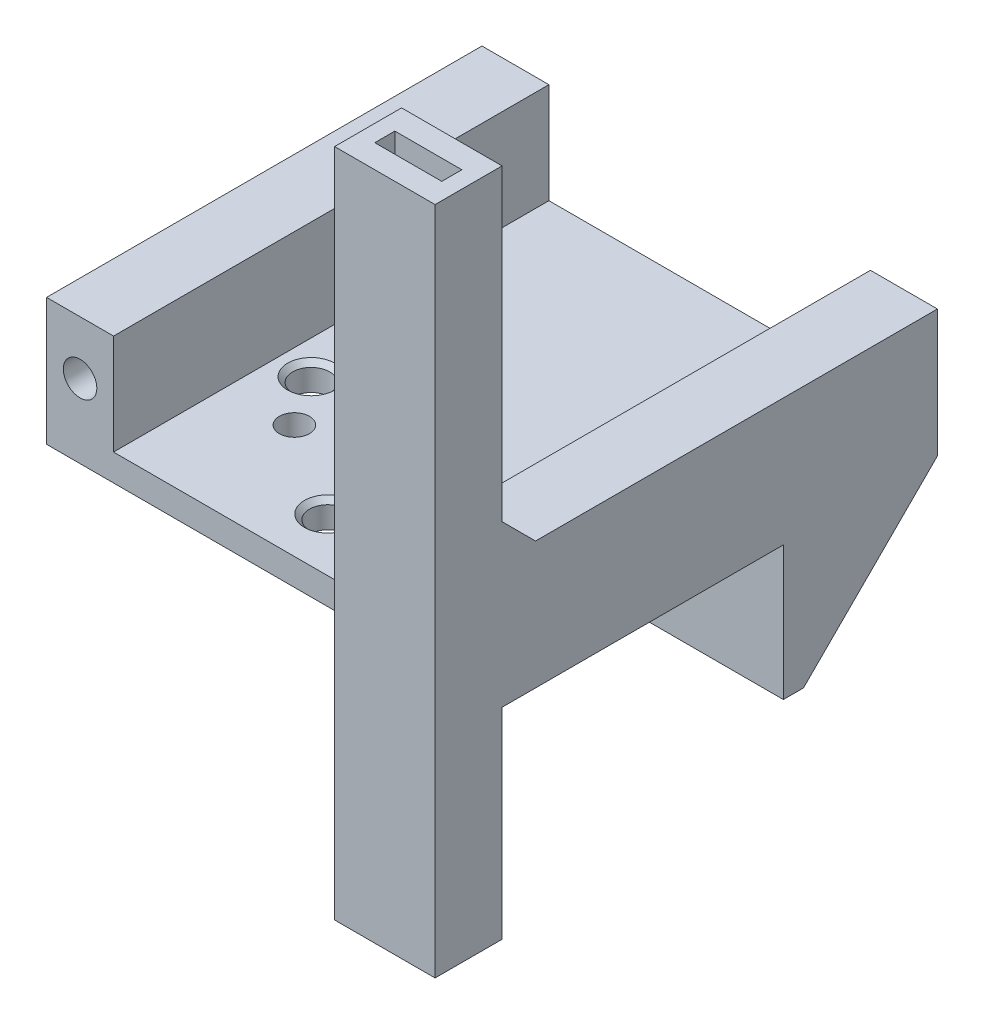
SolidWorks part; units mm, degrees
material "PET"
ref_plane "Front Plane" through (0, 0, 0) normal (0, 0, 1) x (1, 0, 0)
ref_plane "Top Plane" through (0, 0, 0) normal (0, 1, 0) x (1, 0, 0)
ref_plane "Right Plane" through (0, 0, 0) normal (1, 0, 0) x (0, 0, -1)
sketch "Sketch1" plane through (0, 0, 0) normal (0, 1, 0) x (1, 0, 0)
  line L0 (-30, 15) -> (30, 15) construction
  line L2 (-34, 0) -> (-34, 40)
  line L3 (-34, 40) -> (34, 40)
  line L4 (34, 0) -> (34, 40)
  line L5 (0, 0) -> (34, 40) construction
  line L6 (-34, 40) -> (0, 0) construction
  line L7 (-34, 22.5) -> (34, 22.5) construction
  line L8 (-34, 0) -> (-34, -2)
  line L11 (-34, -2) -> (34, -2)
  line L12 (34, -2) -> (34, 0)
  line L13 (-34, 0) -> (34, 0) construction
  line L14 (0, 0) -> (0, 27.8808) construction
  circle A0 centre (-19, 22.5) radius 2.75
  circle A1 centre (19, 22.5) radius 2.75
  circle A3 centre (-14, 15) radius 2.25
  circle A4 centre (14, 15) radius 2.25
  circle A6 centre (0, 6) radius 2.75
  point P0 (0, 0)
  dimension "D5" = 5.5
  dimension "D6" = 5.5
  dimension "D7" = 5.5
  dimension "D8" = 4.5
  dimension "D9" = 4.5
  dimension "D10" = 20
  dimension "D11" = 20
  dimension "D13" = 6
  dimension "D21" = 15
  dimension "D2" = 68
  dimension "D3" = 2
  dimension "D4" = 17.5
  dimension "D12" = 25
  dimension "D17" = 40
  dimension "D18" = 34
  dimension "D20" = 15
extrude "Boss-Extrude1" add sketch "Sketch1" along normal blind 4
sketch "Sketch3" plane through (0, 4, 0) normal (0, 1, 0) x (1, 0, 0)
  line L0 (-34, -2) -> (34, -2) construction
  line L1 (-34, 40) -> (-24, 40)
  line L2 (-34, 40) -> (-34, -2)
  line L3 (-34, -2) -> (-24, -2)
  line L4 (-24, 40) -> (-24, -2)
  line L5 (34, 40) -> (24, 40)
  line L6 (34, 40) -> (34, -2)
  line L7 (34, -2) -> (24, -2)
  line L8 (24, 40) -> (24, -2)
  dimension "D1" = 10
  dimension "D3" = 10
extrude "Boss-Extrude3" add sketch "Sketch3" along normal blind 15
sketch "Sketch4" plane through (0, 0, -40) normal (0, 0, -1) x (-1, 0, 0)
  line L0 (-24, 19) -> (-34, 3) construction
  line L1 (24, 19) -> (34, 19) construction
  line L2 (24, 19) -> (34, 3) construction
  line L4 (-34, 19) -> (-24, 19) construction
  line L5 (-34, 19) -> (-34, 0) construction
  line L6 (34, 19) -> (34, 0) construction
  circle A0 centre (-29, 11) radius 2.5
  circle A1 centre (29, 11) radius 2.5
  dimension "D3" = 5
  dimension "D4" = 5
  dimension "D5" = 8
  dimension "D1" = 8
extrude "Cut-Extrude1" cut sketch "Sketch4" against normal through all
chamfer "Chamfer1" distance 0.75 angle 45 3 edges at (-19, 4, -19.75) (19, 4, -19.75) (0, 4, -3.25)
sketch "Sketch8" plane through (0, 0, 0) normal (0, -1, 0) x (1, 0, 0)
  line L1 (34, 2) -> (19, 2)
  line L2 (34, 2) -> (34, 12)
  line L3 (34, 12) -> (19, 12)
  line L4 (19, 2) -> (19, 12)
  dimension "D1" = 10
  dimension "D2" = 15
extrude "Boss-Extrude5" add sketch "Sketch8" against normal blind 70 and the other way blind 30
sketch "Sketch10" plane through (0, 70, 0) normal (0, 1, 0) x (1, 0, 0)
  line L0 (19, -12) -> (34, -2) construction
  line L2 (21.5, -5.5) -> (31.5, -5.5)
  line L3 (21.5, -5.5) -> (21.5, -8.5)
  line L4 (21.5, -8.5) -> (31.5, -8.5)
  line L5 (31.5, -5.5) -> (31.5, -8.5)
  line L6 (21.5, -5.5) -> (31.5, -8.5) construction
  line L7 (21.5, -8.5) -> (31.5, -5.5) construction
  point P4 (26.5, -7)
  dimension "D1" = 10
  dimension "D2" = 3
extrude "Cut-Extrude4" cut sketch "Sketch10" against normal through all
sketch "Sketch11" plane through (0, 0, -40) normal (0, 0, -1) x (-1, 0, 0)
  line L1 (-24, 19) -> (-34, 19)
  line L2 (-24, 19) -> (-24, 0)
  line L3 (-24, 0) -> (-34, 0)
  line L4 (-34, 19) -> (-34, 0)
  line L5 (24, 19) -> (34, 19)
  line L6 (24, 19) -> (24, 0)
  line L7 (24, 0) -> (34, 0)
  line L8 (34, 19) -> (34, 0)
  circle A0 centre (-29, 11) radius 2.5
  circle A1 centre (29, 11) radius 2.5
extrude "Boss-Extrude6" add sketch "Sketch11" along normal blind 23
sketch "Sketch12" plane through (0, 0, -40) normal (0, 0, -1) x (-1, 0, 0)
  line L0 (-24, 0) -> (-24, 4)
  line L1 (-24, 4) -> (24, 4)
  line L2 (24, 4) -> (24, 0)
  line L3 (24, 0) -> (34, 0)
  line L4 (34, 0) -> (34, -20)
  line L5 (34, -20) -> (-34, -20)
  line L6 (-34, -30) -> (-34, 0) construction
  line L7 (-34, -20) -> (-34, 0)
  line L8 (-34, 0) -> (-24, 0)
  dimension "D1" = 20
extrude "Boss-Extrude7" add sketch "Sketch12" along normal blind 3
sketch "Sketch13" plane through (-34, 0, 0) normal (-1, 0, 0) x (0, 0, 1)
  line L0 (-63, 0) -> (-43, -20)
  line L1 (-43, -20) -> (-43, 0)
  line L2 (-43, 0) -> (-63, 0)
extrude "Boss-Extrude8" add sketch "Sketch13" against normal up to surface (10 mm away) up to face at (-24, 7.6667, -34.6667)
sketch "Sketch14" plane through (34, 0, 0) normal (1, 0, 0) x (0, 0, -1)
  line L0 (43, 0) -> (43, -20)
  line L1 (43, -20) -> (63, 0)
  line L2 (63, 0) -> (43, 0)
extrude "Boss-Extrude9" add sketch "Sketch14" against normal up to surface (10 mm away) up to face at (24, 7.6667, -34.6667)
chamfer "Chamfer2" distance 5 angle 45 1 edges at (24, 11.5, 2)
chamfer "Chamfer3" distance 10 angle 45 1 edges at (19, 2, 2)
chamfer "Chamfer4" distance 5 angle 45 1 edges at (26.5, 19, 2)
sketch "Sketch15" plane through (24, 0, 0) normal (-1, 0, 0) x (0, 0, 1)
  line L0 (-43, -20) -> (-43, 4)
  line L1 (-43, 4) -> (-63, 4)
  line L2 (-63, 0) -> (-63, 19) construction
  line L3 (-63, 4) -> (-63, 0)
  line L4 (-63, 0) -> (-43, -20)
extrude "Boss-Extrude10" add sketch "Sketch15" along normal up to next
